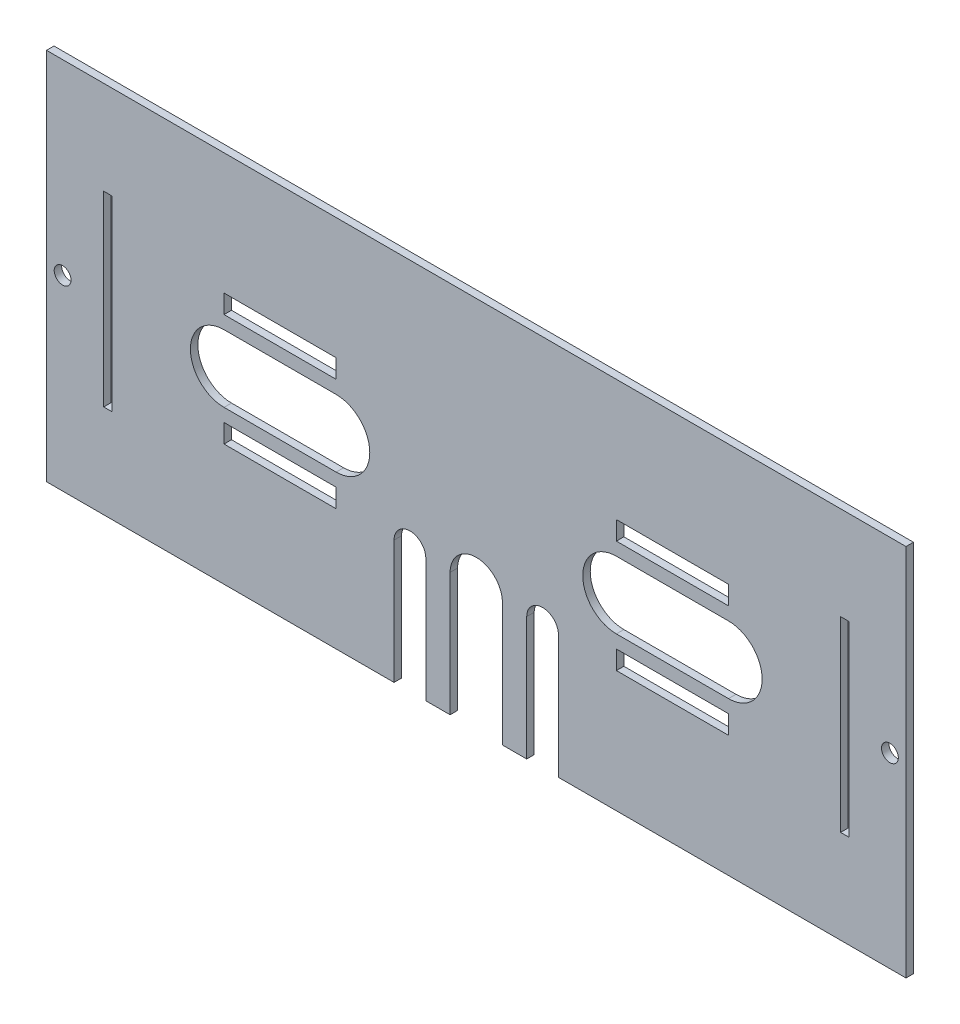
SolidWorks part; units mm, degrees
ref_plane "前视基准面" through (0, 0, 0) normal (0, 0, 1) x (1, 0, 0)
ref_plane "上视基准面" through (0, 0, 0) normal (0, 1, 0) x (1, 0, 0)
ref_plane "右视基准面" through (0, 0, 0) normal (1, 0, 0) x (0, 0, -1)
sketch "草图1" plane through (0, 0, 0) normal (0, 0, 1) x (1, 0, 0)
  line L1 (-49.0448, 20.924) -> (180.9552, 20.924)
  line L2 (-49.0448, 20.924) -> (-49.0448, -79.076)
  line L3 (-49.0448, -79.076) -> (180.9552, -79.076)
  line L4 (180.9552, 20.924) -> (180.9552, -79.076)
  dimension "D1" = 100
  dimension "D2" = 230
extrude "凸台-拉伸1" add sketch "草图1" along normal blind 2
sketch "草图3" plane through (0, 0, 0) normal (0, 0, 1) x (1, 0, 0)
  line L0 (-49.0448, 20.924) -> (-49.0448, -79.076) construction
  line L1 (-33.7448, -4.076) -> (-31.5448, -4.076)
  line L2 (-33.7448, -4.076) -> (-33.7448, -54.076)
  line L3 (-33.7448, -54.076) -> (-31.5448, -54.076)
  line L4 (-31.5448, -4.076) -> (-31.5448, -54.076)
  line L5 (-32.6448, -54.076) -> (-32.6448, -4.076) construction
  line L6 (-33.7448, -29.076) -> (-31.5448, -29.076) construction
  line L7 (180.9552, 20.924) -> (-49.0448, 20.924) construction
  line L8 (65.9552, 82.5756) -> (65.9552, 20.924) construction
  line L9 (65.9552, 20.924) -> (65.9552, -17.9618) construction
  line L10 (-56.6463, -29.076) -> (16.0347, -29.076) construction
  line L11 (16.0347, -29.076) -> (128.3085, -29.076) construction
  line L12 (-1.5448, -44.076) -> (28.4552, -44.076) construction
  line L13 (-1.5448, -11.576) -> (28.4552, -11.576)
  line L14 (-1.5448, -11.576) -> (-1.5448, -16.576)
  line L15 (-1.5448, -16.576) -> (28.4552, -16.576)
  line L16 (28.4552, -11.576) -> (28.4552, -16.576)
  line L17 (13.4552, -16.576) -> (13.4552, -11.576) construction
  line L18 (-1.5448, -14.076) -> (28.4552, -14.076) construction
  line L19 (-1.5448, -20.076) -> (28.4552, -20.076)
  line L21 (-1.5448, -38.076) -> (28.4552, -38.076)
  line L23 (13.4552, -38.076) -> (13.4552, -20.076) construction
  line L24 (-10.6742, -29.076) -> (32.0973, -29.076) construction
  line L25 (13.4552, -41.576) -> (13.4552, -46.576) construction
  line L26 (28.4552, -46.576) -> (28.4552, -41.576)
  line L27 (-1.5448, -41.576) -> (28.4552, -41.576)
  line L28 (-1.5448, -46.576) -> (-1.5448, -41.576)
  line L29 (-1.5448, -46.576) -> (28.4552, -46.576)
  line L30 (118.4552, -41.576) -> (118.4552, -46.576) construction
  line L31 (142.5847, -29.076) -> (99.8132, -29.076) construction
  line L32 (118.4552, -38.076) -> (118.4552, -20.076) construction
  line L33 (133.4552, -14.076) -> (103.4552, -14.076) construction
  line L34 (118.4552, -16.576) -> (118.4552, -11.576) construction
  line L35 (133.4552, -44.076) -> (103.4552, -44.076) construction
  line L36 (165.6552, -29.076) -> (163.4552, -29.076) construction
  line L37 (164.5552, -54.076) -> (164.5552, -4.076) construction
  line L38 (133.4552, -46.576) -> (103.4552, -46.576)
  line L39 (133.4552, -46.576) -> (133.4552, -41.576)
  line L40 (133.4552, -41.576) -> (103.4552, -41.576)
  line L41 (103.4552, -46.576) -> (103.4552, -41.576)
  line L42 (133.4552, -38.076) -> (103.4552, -38.076)
  line L43 (133.4552, -20.076) -> (103.4552, -20.076)
  line L44 (103.4552, -11.576) -> (103.4552, -16.576)
  line L45 (133.4552, -16.576) -> (103.4552, -16.576)
  line L46 (133.4552, -11.576) -> (133.4552, -16.576)
  line L47 (133.4552, -11.576) -> (103.4552, -11.576)
  line L48 (163.4552, -4.076) -> (163.4552, -54.076)
  line L49 (165.6552, -54.076) -> (163.4552, -54.076)
  line L50 (165.6552, -4.076) -> (165.6552, -54.076)
  line L51 (165.6552, -4.076) -> (163.4552, -4.076)
  line L52 (-49.0448, -79.076) -> (180.9552, -79.076) construction
  arc A0 (28.4552, -20.076) -> (28.4552, -38.076) centre (28.4552, -29.076) cw
  arc A1 (-1.5448, -20.076) -> (-1.5448, -38.076) centre (-1.5448, -29.076) ccw
  arc A2 (133.4552, -20.076) -> (133.4552, -38.076) centre (133.4552, -29.076) cw
  arc A3 (103.4552, -20.076) -> (103.4552, -38.076) centre (103.4552, -29.076) ccw
  point P38 (13.4552, -44.076)
  point P73 (118.4552, -29.076)
  point P74 (164.5552, -29.076)
  point P75 (118.4552, -14.076)
  point P76 (118.4552, -44.076)
  point P165 (13.4552, -14.076)
  point P364 (-32.6448, -29.076)
  point P526 (13.4552, -29.076)
  dimension "D9" = 9
  dimension "D10" = 9
  dimension "D3" = 50
  dimension "D4" = 2.2
  dimension "D5" = 12.5
  dimension "D6" = 5
  dimension "D7" = 37.5
  dimension "D8" = 30
  dimension "D11" = 30
  dimension "D12" = 18
  dimension "D13" = 37.5
  dimension "D14" = 16.4
  dimension "D15" = 50
extrude "切除-拉伸2" cut sketch "草图3" against normal blind 2 and the other way blind 2
sketch "草图4" plane through (0, 0, 0) normal (0, 0, 1) x (1, 0, 0)
  line L0 (-49.0448, -79.076) -> (180.9552, -79.076) construction
  line L2 (43.9552, -46.076) -> (43.9552, -79.076)
  line L3 (43.9552, -79.076) -> (52.4552, -79.076)
  line L4 (52.4552, -46.076) -> (52.4552, -79.076)
  line L5 (48.2052, -79.076) -> (48.2052, -46.076) construction
  line L6 (43.9552, -62.576) -> (52.4552, -62.576) construction
  line L7 (65.9552, 49.5064) -> (65.9552, -10.9661) construction
  line L8 (87.9552, -62.576) -> (79.4552, -62.576) construction
  line L9 (180.9552, 20.924) -> (-49.0448, 20.924) construction
  line L12 (58.9552, -46.076) -> (58.9552, -79.076)
  line L13 (58.9552, -79.076) -> (72.9552, -79.076)
  line L14 (72.9552, -46.076) -> (72.9552, -79.076)
  line L15 (65.9552, -79.076) -> (65.9552, -46.076) construction
  line L16 (58.9552, -62.576) -> (72.9552, -62.576) construction
  line L17 (83.7052, -79.076) -> (83.7052, -46.076) construction
  line L18 (79.4552, -46.076) -> (79.4552, -79.076)
  line L19 (87.9552, -79.076) -> (79.4552, -79.076)
  line L20 (87.9552, -46.076) -> (87.9552, -79.076)
  arc A0 (43.9552, -46.076) -> (52.4552, -46.076) centre (48.2052, -46.076) cw
  arc A1 (58.9552, -46.076) -> (72.9552, -46.076) centre (65.9552, -46.076) cw
  arc A2 (87.9552, -46.076) -> (79.4552, -46.076) centre (83.7052, -46.076) ccw
  point P11 (65.9552, 20.924)
  point P27 (83.7052, -62.576)
  point P155 (65.9552, -62.576)
  point P332 (48.2052, -62.576)
  dimension "D5" = 4.25
  dimension "D6" = 7
  dimension "D1" = 33
  dimension "D2" = 8.5
  dimension "D3" = 6.5
  dimension "D4" = 14
  dimension "D7" = 33
extrude "切除-拉伸3" cut sketch "草图4" against normal blind 2 and the other way blind 2
sketch "草图5" plane through (0, 0, 0) normal (0, 0, 1) x (1, 0, 0)
  line L0 (-49.0448, 20.924) -> (-49.0448, -79.076) construction
  line L1 (180.9552, -79.076) -> (180.9552, 20.924) construction
  line L2 (-49.0448, -29.076) -> (180.9552, -29.076) construction
  line L3 (-33.7448, -4.076) -> (-33.7448, -54.076) construction
  line L4 (180.9552, 20.924) -> (-49.0448, 20.924) construction
  line L5 (65.9552, 20.924) -> (65.9552, -29.8023) construction
  circle A0 centre (-44.7448, -29.076) radius 2.25
  circle A1 centre (176.6552, -29.076) radius 2.25
  point P2 (-49.0448, -29.076)
  point P3 (180.9552, -29.076)
  point P10 (65.9552, -29.076)
  point P13 (65.9552, 20.924)
  dimension "D1" = 4.5
  dimension "D2" = 11
extrude "切除-拉伸8" cut sketch "草图5" against normal blind 2 draft 1 and the other way blind 2
